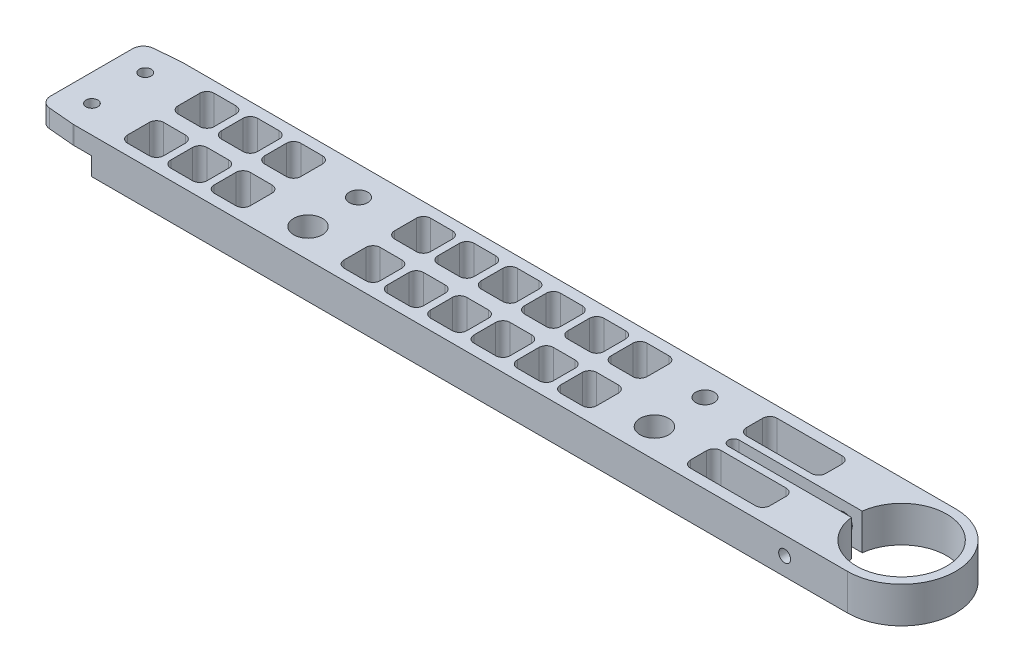
SolidWorks part; units mm, degrees
material "3.1355 (EN-AW 2024)"
ref_plane "Front" through (0, 0, 0) normal (0, 0, 1) x (1, 0, 0)
ref_plane "Top" through (0, 0, 0) normal (0, 1, 0) x (1, 0, 0)
ref_plane "Right" through (0, 0, 0) normal (1, 0, 0) x (0, 0, -1)
sketch "Эскиз1" plane through (0, 0, 0) normal (0, 1, 0) x (1, 0, 0)
  line L0 (240, 15) -> (15, 15) construction
  line L1 (15, 0) -> (240, 0)
  line L2 (0, 0) -> (0, 30) construction
  line L3 (15, 30) -> (240, 30)
  line L4 (240, 0) -> (240, 30)
  line L5 (0, 0) -> (15, 0) construction
  line L6 (0, 0.8749) -> (0, 29.1251)
  line L7 (15, 30) -> (10, 30)
  line L8 (10, 30) -> (0, 29.1251)
  line L9 (10, 0) -> (0, 0.8749)
  line L10 (15, 0) -> (10, 0)
  line L11 (0, 30) -> (1, 30) construction
  line L12 (1, 30) -> (1, 29.2126) construction
  arc A0 (15, 30) -> (15, 0) centre (15, 15) ccw construction
  point P13 (0, 15)
  dimension "D1" = 30
  dimension "D2" = 240
  dimension "D4" = 5
  dimension "D5" = 85
extrude "Бобышка-Вытянуть1" add sketch "Эскиз1" along normal blind 10
sketch "Эскиз4" plane through (0, 0, 0) normal (0, -1, 0) x (1, 0, 0)
  line L0 (10, 0) -> (240, 0) construction
  line L1 (0, -30) -> (15, -30)
  line L2 (0, -30) -> (0, 0)
  line L3 (0, 0) -> (15, 0)
  line L4 (15, -30) -> (15, 0)
  line L5 (0, -29.1251) -> (0, -0.8749) construction
  line L6 (240, -30) -> (10, -30) construction
  dimension "D1" = 15
extrude "Вырез-Вытянуть2" cut sketch "Эскиз4" against normal blind 5
fillet "Скругление1" radius 3 4 edges at (10, 7.5, -30) (0, 7.5, -29.1251) (0, 7.5, -0.8749) (10, 7.5, 0)
sketch "Эскиз5" plane through (0, 0, 0) normal (0, -1, 0) x (1, 0, 0)
  line L0 (240, -15) -> (210, -15) construction
  line L1 (240, 0) -> (240, -30) construction
  line L2 (15, -15) -> (20, -15) construction
  line L3 (15, -30) -> (15, 0) construction
  line L4 (240, -30) -> (15, -30) construction
  line L5 (22, -17) -> (28, -17)
  line L6 (20, -19) -> (20, -25)
  line L7 (22, -27) -> (28, -27)
  line L8 (30, -19) -> (30, -25)
  line L9 (20, -17) -> (30, -27) construction
  line L10 (20, -27) -> (30, -17) construction
  line L11 (34, -17) -> (40, -17)
  line L12 (32, -19) -> (32, -25)
  line L13 (34, -27) -> (40, -27)
  line L14 (42, -19) -> (42, -25)
  line L15 (32, -17) -> (42, -27) construction
  line L16 (32, -27) -> (42, -17) construction
  line L17 (46, -17) -> (52, -17)
  line L18 (44, -19) -> (44, -25)
  line L19 (46, -27) -> (52, -27)
  line L20 (54, -19) -> (54, -25)
  line L21 (44, -17) -> (54, -27) construction
  line L22 (44, -27) -> (54, -17) construction
  line L23 (58, -17) -> (64, -17)
  line L24 (56, -19) -> (56, -25)
  line L25 (58, -27) -> (64, -27)
  line L26 (66, -19) -> (66, -25)
  line L27 (56, -17) -> (66, -27) construction
  line L28 (56, -27) -> (66, -17) construction
  line L29 (70, -17) -> (76, -17)
  line L30 (68, -19) -> (68, -25)
  line L31 (70, -27) -> (76, -27)
  line L32 (78, -19) -> (78, -25)
  line L33 (68, -17) -> (78, -27) construction
  line L34 (68, -27) -> (78, -17) construction
  line L35 (82, -17) -> (88, -17)
  line L36 (80, -19) -> (80, -25)
  line L37 (82, -27) -> (88, -27)
  line L38 (90, -19) -> (90, -25)
  line L39 (80, -17) -> (90, -27) construction
  line L40 (80, -27) -> (90, -17) construction
  line L41 (94, -17) -> (100, -17)
  line L42 (92, -19) -> (92, -25)
  line L43 (94, -27) -> (100, -27)
  line L44 (102, -19) -> (102, -25)
  line L45 (92, -17) -> (102, -27) construction
  line L46 (92, -27) -> (102, -17) construction
  line L47 (106, -17) -> (112, -17)
  line L48 (104, -19) -> (104, -25)
  line L49 (106, -27) -> (112, -27)
  line L50 (114, -19) -> (114, -25)
  line L51 (104, -17) -> (114, -27) construction
  line L52 (104, -27) -> (114, -17) construction
  line L53 (118, -17) -> (124, -17)
  line L54 (116, -19) -> (116, -25)
  line L55 (118, -27) -> (124, -27)
  line L56 (126, -19) -> (126, -25)
  line L57 (116, -17) -> (126, -27) construction
  line L58 (116, -27) -> (126, -17) construction
  line L59 (130, -17) -> (136, -17)
  line L60 (128, -19) -> (128, -25)
  line L61 (130, -27) -> (136, -27)
  line L62 (138, -19) -> (138, -25)
  line L63 (128, -17) -> (138, -27) construction
  line L64 (128, -27) -> (138, -17) construction
  line L65 (142, -17) -> (148, -17)
  line L66 (140, -19) -> (140, -25)
  line L67 (142, -27) -> (148, -27)
  line L68 (150, -19) -> (150, -25)
  line L69 (140, -17) -> (150, -27) construction
  line L70 (140, -27) -> (150, -17) construction
  line L71 (154, -17) -> (160, -17)
  line L72 (152, -19) -> (152, -25)
  line L73 (154, -27) -> (160, -27)
  line L74 (162, -19) -> (162, -25)
  line L75 (152, -17) -> (162, -27) construction
  line L76 (152, -27) -> (162, -17) construction
  line L77 (166, -17) -> (172, -17)
  line L78 (164, -19) -> (164, -25)
  line L79 (166, -27) -> (172, -27)
  line L80 (174, -19) -> (174, -25)
  line L81 (164, -17) -> (174, -27) construction
  line L82 (164, -27) -> (174, -17) construction
  line L83 (178, -17) -> (184, -17)
  line L84 (176, -19) -> (176, -25)
  line L85 (178, -27) -> (184, -27)
  line L86 (186, -19) -> (186, -25)
  line L87 (176, -17) -> (186, -27) construction
  line L88 (176, -27) -> (186, -17) construction
  line L89 (190, -17) -> (196, -17)
  line L90 (188, -19) -> (188, -25)
  line L91 (190, -27) -> (196, -27)
  line L92 (198, -19) -> (198, -25)
  line L93 (188, -17) -> (198, -27) construction
  line L94 (188, -27) -> (198, -17) construction
  line L95 (202, -17) -> (208, -17)
  line L96 (200, -19) -> (200, -25)
  line L97 (202, -27) -> (208, -27)
  line L98 (210, -19) -> (210, -25)
  line L99 (200, -17) -> (210, -27) construction
  line L100 (200, -27) -> (210, -17) construction
  line L101 (25, -22) -> (37, -22) construction
  line L102 (25, -8) -> (37, -8) construction
  line L103 (200, -3) -> (210, -13) construction
  line L104 (200, -13) -> (210, -3) construction
  line L105 (188, -3) -> (198, -13) construction
  line L106 (188, -13) -> (198, -3) construction
  line L107 (176, -3) -> (186, -13) construction
  line L108 (176, -13) -> (186, -3) construction
  line L109 (164, -3) -> (174, -13) construction
  line L110 (164, -13) -> (174, -3) construction
  line L111 (152, -3) -> (162, -13) construction
  line L112 (152, -13) -> (162, -3) construction
  line L113 (140, -3) -> (150, -13) construction
  line L114 (140, -13) -> (150, -3) construction
  line L115 (128, -3) -> (138, -13) construction
  line L116 (128, -13) -> (138, -3) construction
  line L117 (116, -3) -> (126, -13) construction
  line L118 (116, -13) -> (126, -3) construction
  line L119 (104, -3) -> (114, -13) construction
  line L120 (104, -13) -> (114, -3) construction
  line L121 (92, -3) -> (102, -13) construction
  line L122 (92, -13) -> (102, -3) construction
  line L123 (80, -3) -> (90, -13) construction
  line L124 (80, -13) -> (90, -3) construction
  line L125 (68, -3) -> (78, -13) construction
  line L126 (68, -13) -> (78, -3) construction
  line L127 (56, -3) -> (66, -13) construction
  line L128 (56, -13) -> (66, -3) construction
  line L129 (44, -3) -> (54, -13) construction
  line L130 (44, -13) -> (54, -3) construction
  line L131 (32, -3) -> (42, -13) construction
  line L132 (32, -13) -> (42, -3) construction
  line L133 (20, -3) -> (30, -13) construction
  line L134 (20, -13) -> (30, -3) construction
  line L135 (210, -11) -> (210, -5)
  line L136 (202, -3) -> (208, -3)
  line L137 (200, -11) -> (200, -5)
  line L138 (202, -13) -> (208, -13)
  line L139 (198, -11) -> (198, -5)
  line L140 (190, -3) -> (196, -3)
  line L141 (188, -11) -> (188, -5)
  line L142 (190, -13) -> (196, -13)
  line L143 (186, -11) -> (186, -5)
  line L144 (178, -3) -> (184, -3)
  line L145 (176, -11) -> (176, -5)
  line L146 (178, -13) -> (184, -13)
  line L147 (174, -11) -> (174, -5)
  line L148 (166, -3) -> (172, -3)
  line L149 (164, -11) -> (164, -5)
  line L150 (166, -13) -> (172, -13)
  line L151 (162, -11) -> (162, -5)
  line L152 (154, -3) -> (160, -3)
  line L153 (152, -11) -> (152, -5)
  line L154 (154, -13) -> (160, -13)
  line L155 (150, -11) -> (150, -5)
  line L156 (142, -3) -> (148, -3)
  line L157 (140, -11) -> (140, -5)
  line L158 (142, -13) -> (148, -13)
  line L159 (138, -11) -> (138, -5)
  line L160 (130, -3) -> (136, -3)
  line L161 (128, -11) -> (128, -5)
  line L162 (130, -13) -> (136, -13)
  line L163 (126, -11) -> (126, -5)
  line L164 (118, -3) -> (124, -3)
  line L165 (116, -11) -> (116, -5)
  line L166 (118, -13) -> (124, -13)
  line L167 (114, -11) -> (114, -5)
  line L168 (106, -3) -> (112, -3)
  line L169 (104, -11) -> (104, -5)
  line L170 (106, -13) -> (112, -13)
  line L171 (102, -11) -> (102, -5)
  line L172 (94, -3) -> (100, -3)
  line L173 (92, -11) -> (92, -5)
  line L174 (94, -13) -> (100, -13)
  line L175 (90, -11) -> (90, -5)
  line L176 (82, -3) -> (88, -3)
  line L177 (80, -11) -> (80, -5)
  line L178 (82, -13) -> (88, -13)
  line L179 (78, -11) -> (78, -5)
  line L180 (70, -3) -> (76, -3)
  line L181 (68, -11) -> (68, -5)
  line L182 (70, -13) -> (76, -13)
  line L183 (66, -11) -> (66, -5)
  line L184 (58, -3) -> (64, -3)
  line L185 (56, -11) -> (56, -5)
  line L186 (58, -13) -> (64, -13)
  line L187 (54, -11) -> (54, -5)
  line L188 (46, -3) -> (52, -3)
  line L189 (44, -11) -> (44, -5)
  line L190 (46, -13) -> (52, -13)
  line L191 (42, -11) -> (42, -5)
  line L192 (34, -3) -> (40, -3)
  line L193 (32, -11) -> (32, -5)
  line L194 (34, -13) -> (40, -13)
  line L195 (30, -11) -> (30, -5)
  line L196 (22, -3) -> (28, -3)
  line L197 (20, -11) -> (20, -5)
  line L198 (22, -13) -> (28, -13)
  arc A0 (20, -25) -> (22, -27) centre (22, -25) ccw
  arc A1 (30, -25) -> (28, -27) centre (28, -25) cw
  arc A2 (28, -17) -> (30, -19) centre (28, -19) cw
  arc A3 (22, -17) -> (20, -19) centre (22, -19) ccw
  arc A4 (32, -25) -> (34, -27) centre (34, -25) ccw
  arc A5 (42, -25) -> (40, -27) centre (40, -25) cw
  arc A6 (40, -17) -> (42, -19) centre (40, -19) cw
  arc A7 (34, -17) -> (32, -19) centre (34, -19) ccw
  arc A8 (44, -25) -> (46, -27) centre (46, -25) ccw
  arc A9 (54, -25) -> (52, -27) centre (52, -25) cw
  arc A10 (52, -17) -> (54, -19) centre (52, -19) cw
  arc A11 (46, -17) -> (44, -19) centre (46, -19) ccw
  arc A12 (56, -25) -> (58, -27) centre (58, -25) ccw
  arc A13 (66, -25) -> (64, -27) centre (64, -25) cw
  arc A14 (64, -17) -> (66, -19) centre (64, -19) cw
  arc A15 (58, -17) -> (56, -19) centre (58, -19) ccw
  arc A16 (68, -25) -> (70, -27) centre (70, -25) ccw
  arc A17 (78, -25) -> (76, -27) centre (76, -25) cw
  arc A18 (76, -17) -> (78, -19) centre (76, -19) cw
  arc A19 (70, -17) -> (68, -19) centre (70, -19) ccw
  arc A20 (80, -25) -> (82, -27) centre (82, -25) ccw
  arc A21 (90, -25) -> (88, -27) centre (88, -25) cw
  arc A22 (88, -17) -> (90, -19) centre (88, -19) cw
  arc A23 (82, -17) -> (80, -19) centre (82, -19) ccw
  arc A24 (92, -25) -> (94, -27) centre (94, -25) ccw
  arc A25 (102, -25) -> (100, -27) centre (100, -25) cw
  arc A26 (100, -17) -> (102, -19) centre (100, -19) cw
  arc A27 (94, -17) -> (92, -19) centre (94, -19) ccw
  arc A28 (104, -25) -> (106, -27) centre (106, -25) ccw
  arc A29 (114, -25) -> (112, -27) centre (112, -25) cw
  arc A30 (112, -17) -> (114, -19) centre (112, -19) cw
  arc A31 (106, -17) -> (104, -19) centre (106, -19) ccw
  arc A32 (116, -25) -> (118, -27) centre (118, -25) ccw
  arc A33 (126, -25) -> (124, -27) centre (124, -25) cw
  arc A34 (124, -17) -> (126, -19) centre (124, -19) cw
  arc A35 (118, -17) -> (116, -19) centre (118, -19) ccw
  arc A36 (128, -25) -> (130, -27) centre (130, -25) ccw
  arc A37 (138, -25) -> (136, -27) centre (136, -25) cw
  arc A38 (136, -17) -> (138, -19) centre (136, -19) cw
  arc A39 (130, -17) -> (128, -19) centre (130, -19) ccw
  arc A40 (140, -25) -> (142, -27) centre (142, -25) ccw
  arc A41 (150, -25) -> (148, -27) centre (148, -25) cw
  arc A42 (148, -17) -> (150, -19) centre (148, -19) cw
  arc A43 (142, -17) -> (140, -19) centre (142, -19) ccw
  arc A44 (152, -25) -> (154, -27) centre (154, -25) ccw
  arc A45 (162, -25) -> (160, -27) centre (160, -25) cw
  arc A46 (160, -17) -> (162, -19) centre (160, -19) cw
  arc A47 (154, -17) -> (152, -19) centre (154, -19) ccw
  arc A48 (164, -25) -> (166, -27) centre (166, -25) ccw
  arc A49 (174, -25) -> (172, -27) centre (172, -25) cw
  arc A50 (172, -17) -> (174, -19) centre (172, -19) cw
  arc A51 (166, -17) -> (164, -19) centre (166, -19) ccw
  arc A52 (176, -25) -> (178, -27) centre (178, -25) ccw
  arc A53 (186, -25) -> (184, -27) centre (184, -25) cw
  arc A54 (184, -17) -> (186, -19) centre (184, -19) cw
  arc A55 (178, -17) -> (176, -19) centre (178, -19) ccw
  arc A56 (188, -25) -> (190, -27) centre (190, -25) ccw
  arc A57 (198, -25) -> (196, -27) centre (196, -25) cw
  arc A58 (196, -17) -> (198, -19) centre (196, -19) cw
  arc A59 (190, -17) -> (188, -19) centre (190, -19) ccw
  arc A60 (200, -25) -> (202, -27) centre (202, -25) ccw
  arc A61 (210, -25) -> (208, -27) centre (208, -25) cw
  arc A62 (208, -17) -> (210, -19) centre (208, -19) cw
  arc A63 (202, -17) -> (200, -19) centre (202, -19) ccw
  arc A64 (202, -13) -> (200, -11) centre (202, -11) cw
  arc A65 (208, -13) -> (210, -11) centre (208, -11) ccw
  arc A66 (210, -5) -> (208, -3) centre (208, -5) ccw
  arc A67 (200, -5) -> (202, -3) centre (202, -5) cw
  arc A68 (190, -13) -> (188, -11) centre (190, -11) cw
  arc A69 (196, -13) -> (198, -11) centre (196, -11) ccw
  arc A70 (198, -5) -> (196, -3) centre (196, -5) ccw
  arc A71 (188, -5) -> (190, -3) centre (190, -5) cw
  arc A72 (178, -13) -> (176, -11) centre (178, -11) cw
  arc A73 (184, -13) -> (186, -11) centre (184, -11) ccw
  arc A74 (186, -5) -> (184, -3) centre (184, -5) ccw
  arc A75 (176, -5) -> (178, -3) centre (178, -5) cw
  arc A76 (166, -13) -> (164, -11) centre (166, -11) cw
  arc A77 (172, -13) -> (174, -11) centre (172, -11) ccw
  arc A78 (174, -5) -> (172, -3) centre (172, -5) ccw
  arc A79 (164, -5) -> (166, -3) centre (166, -5) cw
  arc A80 (154, -13) -> (152, -11) centre (154, -11) cw
  arc A81 (160, -13) -> (162, -11) centre (160, -11) ccw
  arc A82 (162, -5) -> (160, -3) centre (160, -5) ccw
  arc A83 (152, -5) -> (154, -3) centre (154, -5) cw
  arc A84 (142, -13) -> (140, -11) centre (142, -11) cw
  arc A85 (148, -13) -> (150, -11) centre (148, -11) ccw
  arc A86 (150, -5) -> (148, -3) centre (148, -5) ccw
  arc A87 (140, -5) -> (142, -3) centre (142, -5) cw
  arc A88 (130, -13) -> (128, -11) centre (130, -11) cw
  arc A89 (136, -13) -> (138, -11) centre (136, -11) ccw
  arc A90 (138, -5) -> (136, -3) centre (136, -5) ccw
  arc A91 (128, -5) -> (130, -3) centre (130, -5) cw
  arc A92 (118, -13) -> (116, -11) centre (118, -11) cw
  arc A93 (124, -13) -> (126, -11) centre (124, -11) ccw
  arc A94 (126, -5) -> (124, -3) centre (124, -5) ccw
  arc A95 (116, -5) -> (118, -3) centre (118, -5) cw
  arc A96 (106, -13) -> (104, -11) centre (106, -11) cw
  arc A97 (112, -13) -> (114, -11) centre (112, -11) ccw
  arc A98 (114, -5) -> (112, -3) centre (112, -5) ccw
  arc A99 (104, -5) -> (106, -3) centre (106, -5) cw
  arc A100 (94, -13) -> (92, -11) centre (94, -11) cw
  arc A101 (100, -13) -> (102, -11) centre (100, -11) ccw
  arc A102 (102, -5) -> (100, -3) centre (100, -5) ccw
  arc A103 (92, -5) -> (94, -3) centre (94, -5) cw
  arc A104 (82, -13) -> (80, -11) centre (82, -11) cw
  arc A105 (88, -13) -> (90, -11) centre (88, -11) ccw
  arc A106 (90, -5) -> (88, -3) centre (88, -5) ccw
  arc A107 (80, -5) -> (82, -3) centre (82, -5) cw
  arc A108 (70, -13) -> (68, -11) centre (70, -11) cw
  arc A109 (76, -13) -> (78, -11) centre (76, -11) ccw
  arc A110 (78, -5) -> (76, -3) centre (76, -5) ccw
  arc A111 (68, -5) -> (70, -3) centre (70, -5) cw
  arc A112 (58, -13) -> (56, -11) centre (58, -11) cw
  arc A113 (64, -13) -> (66, -11) centre (64, -11) ccw
  arc A114 (66, -5) -> (64, -3) centre (64, -5) ccw
  arc A115 (56, -5) -> (58, -3) centre (58, -5) cw
  arc A116 (46, -13) -> (44, -11) centre (46, -11) cw
  arc A117 (52, -13) -> (54, -11) centre (52, -11) ccw
  arc A118 (54, -5) -> (52, -3) centre (52, -5) ccw
  arc A119 (44, -5) -> (46, -3) centre (46, -5) cw
  arc A120 (34, -13) -> (32, -11) centre (34, -11) cw
  arc A121 (40, -13) -> (42, -11) centre (40, -11) ccw
  arc A122 (42, -5) -> (40, -3) centre (40, -5) ccw
  arc A123 (32, -5) -> (34, -3) centre (34, -5) cw
  arc A124 (22, -13) -> (20, -11) centre (22, -11) cw
  arc A125 (28, -13) -> (30, -11) centre (28, -11) ccw
  arc A126 (30, -5) -> (28, -3) centre (28, -5) ccw
  arc A127 (20, -5) -> (22, -3) centre (22, -5) cw
  point P8 (25, -22)
  point P29 (37, -22)
  point P46 (49, -22)
  point P63 (61, -22)
  point P80 (73, -22)
  point P97 (85, -22)
  point P114 (97, -22)
  point P131 (109, -22)
  point P148 (121, -22)
  point P165 (133, -22)
  point P182 (145, -22)
  point P199 (157, -22)
  point P216 (169, -22)
  point P233 (181, -22)
  point P250 (193, -22)
  point P267 (205, -22)
  point P542 (205, -8)
  point P543 (193, -8)
  point P544 (181, -8)
  point P545 (169, -8)
  point P546 (157, -8)
  point P547 (145, -8)
  point P548 (133, -8)
  point P549 (121, -8)
  point P550 (109, -8)
  point P551 (97, -8)
  point P552 (85, -8)
  point P553 (73, -8)
  point P554 (61, -8)
  point P555 (49, -8)
  dimension "D5" = 2
  dimension "D1" = 30
  dimension "D2" = 5
  dimension "D3" = 10
  dimension "D4" = 3
  dimension "D7" = 12
  dimension "D6" = 16
extrude "Вырез-Вытянуть3" cut sketch "Эскиз5" against normal through all
sketch "Эскиз6" plane through (0, 0, 0) normal (0, -1, 0) x (1, 0, 0)
  line L1 (54.9134, -27.789) -> (78.7581, -27.789)
  line L2 (54.9134, -27.789) -> (54.9134, -2.1781)
  line L3 (54.9134, -2.1781) -> (78.7581, -2.1781)
  line L4 (78.7581, -27.789) -> (78.7581, -2.1781)
  line L5 (150.9148, -27.789) -> (175.2011, -27.789)
  line L6 (150.9148, -27.789) -> (150.9148, -2.1781)
  line L7 (150.9148, -2.1781) -> (175.2011, -2.1781)
  line L8 (175.2011, -27.789) -> (175.2011, -2.1781)
extrude "Бобышка-Вытянуть2" add sketch "Эскиз6" against normal through all
sketch "Эскиз7" plane through (0, 0, 0) normal (0, -1, 0) x (1, 0, 0)
  line L0 (54, -22) -> (80, -22) construction
  line L1 (54, -25) -> (54, -19) construction
  line L2 (80, -19) -> (80, -25) construction
  line L3 (54, -8) -> (80, -8) construction
  line L4 (54, -11) -> (54, -5) construction
  line L5 (80, -5) -> (80, -11) construction
  line L6 (176, -8) -> (150, -8) construction
  line L7 (176, -5) -> (176, -11) construction
  line L8 (150, -11) -> (150, -5) construction
  line L9 (176, -22) -> (150, -22) construction
  line L10 (176, -19) -> (176, -25) construction
  line L11 (150, -25) -> (150, -19) construction
  point P12 (67, -8)
  point P13 (67, -22)
  point P26 (163, -8)
  point P27 (163, -22)
hole_wizard "Отверстие обработанное метчиком 1/4-201" positions "Эскиз9" profile "Эскиз8" tap size "1/4-20" standard "Ansi Inch" end condition through all
sketch "Эскиз9" plane through (0, 0, 0) normal (0, -1, 0) x (-1, 0, 0)
  point P0 (-67, 22)
  point P3 (-163, 22)
sketch "Эскиз8" plane through (67, 0, -22) normal (1, 0, 0) x (0, 0, -1)
  line L0 (0, 0) -> (0, 10)
  line L1 (0, 10) -> (2.5527, 10)
  line L2 (2.5527, 10) -> (2.5527, 0)
  line L5 (2.5527, 0) -> (0, 0)
  line L11 (0, -6.35) -> (0, 107.95) construction
  dimension "Диаметр проходного сверла" = 5.1054
  dimension "Глубина проходного сверла" = 10
cosmetic thread "Отверстие резьбы1" parameters "D2"=6.35
cosmetic thread "Отверстие резьбы2" parameters "D2"=6.35
hole_wizard "Отверстие обработанное метчиком 3/8-161" positions "Эскиз11" profile "Эскиз10" tap size "3/8-16" standard "Ansi Inch" end condition through all
sketch "Эскиз11" plane through (0, 0, 0) normal (0, -1, 0) x (-1, 0, 0)
  point P0 (-163, 8)
  point P3 (-67, 8)
sketch "Эскиз10" plane through (163, 0, -8) normal (1, 0, 0) x (0, 0, -1)
  line L0 (0, 0) -> (0, 10)
  line L1 (0, 10) -> (3.9687, 10)
  line L2 (3.9687, 10) -> (3.9687, 0)
  line L5 (3.9687, 0) -> (0, 0)
  line L11 (0, -6.35) -> (0, 107.95) construction
  dimension "Диаметр проходного сверла" = 7.9375
  dimension "Глубина проходного сверла" = 10
cosmetic thread "Отверстие резьбы3" parameters "D2"=9.525
cosmetic thread "Отверстие резьбы4" parameters "D2"=9.525
sketch "Эскиз12" plane through (0, 0, 0) normal (0, -1, 0) x (1, 0, 0)
  line L0 (240, -15) -> (224.5, -15) construction
  line L1 (240, 0) -> (240, -30) construction
  line L2 (224.5, -30) -> (240, -30)
  line L3 (240, -30) -> (240, 0)
  line L4 (240, 0) -> (224.5, 0)
  circle A0 centre (224.5, -15) radius 12.5
  arc A1 (224.5, -30) -> (224.5, 0) centre (224.5, -15) ccw
  dimension "D2" = 25
  dimension "D1" = 15.5
extrude "Вырез-Вытянуть4" cut sketch "Эскиз12" against normal through all
sketch "Эскиз13" plane through (0, 0, 0) normal (0, -1, 0) x (1, 0, 0)
  line L1 (198.8914, -28.2833) -> (210.981, -28.2833)
  line L2 (198.8914, -28.2833) -> (198.8914, -1.8689)
  line L3 (198.8914, -1.8689) -> (210.981, -1.8689)
  line L4 (210.981, -28.2833) -> (210.981, -1.8689)
extrude "Бобышка-Вытянуть3" add sketch "Эскиз13" against normal through all
sketch "Эскиз14" plane through (0, 0, 0) normal (0, -1, 0) x (1, 0, 0)
  line L0 (212, -15) -> (178, -15) construction
  line L1 (178, -15) -> (213.598, -15) construction
  line L2 (178, -13.5) -> (213.598, -13.5)
  line L3 (178, -16.5) -> (213.598, -16.5)
  arc A0 (178, -13.5) -> (178, -16.5) centre (178, -15) ccw
  arc A1 (213.598, -16.5) -> (213.598, -13.5) centre (213.598, -15) ccw
  circle A4 centre (224.5, -15) radius 12.5 construction
  point P5 (195.799, -15)
  dimension "D2" = 1.5
  dimension "D1" = 34
extrude "Вырез-Вытянуть5" cut sketch "Эскиз14" against normal blind 10
sketch "Эскиз15" plane through (0, 0, 0) normal (0, 0, 1) x (1, 0, 0)
  line L0 (212.0903, 5) -> (207.0903, 5) construction
  line L1 (212.0903, 0) -> (212.0903, 10) construction
  dimension "D1" = 5
hole_wizard "Отверстие обработанное метчиком M4x0.71" positions "Эскиз17" profile "Эскиз16" tap size "M4x0.7" standard "Ansi Metric" end condition through all
sketch "Эскиз17" plane through (0, 0, -13.5) normal (0, 0, -1) x (-1, 0, 0)
  point P0 (-207.0903, 5)
sketch "Эскиз16" plane through (207.0903, 5, -13.5) normal (1, 0, 0) x (0, 1, 0)
  line L0 (0, 0) -> (0, 13.5)
  line L1 (0, 13.5) -> (1.65, 13.5)
  line L2 (1.65, 13.5) -> (1.65, 0)
  line L5 (1.65, 0) -> (0, 0)
  line L11 (0, -6.35) -> (0, 107.95) construction
  dimension "Диаметр проходного сверла" = 3.3
  dimension "Глубина проходного сверла" = 13.5
cosmetic thread "Отверстие резьбы5" parameters "D2"=4
hole_wizard "Цековка для винта с внутренним шестигранником M41" positions "Эскиз19" profile "Эскиз18" counterbore size "M4" standard "Ansi Metric" end condition up to next
sketch "Эскиз19" plane through (0, 0, -30) normal (0, 0, -1) x (-1, 0, 0)
  point P0 (-207.0903, 5)
sketch "Эскиз18" plane through (207.0903, 5, -30) normal (1, 0, 0) x (0, 1, 0)
  line L0 (0, 0) -> (0, 13.5)
  line L1 (0, 13.5) -> (2.25, 13.5)
  line L3 (2.25, 13.5) -> (2.25, 4)
  line L4 (2.25, 4) -> (4, 4)
  line L5 (4, 4) -> (4, 0)
  line L7 (4, 0) -> (0, 0)
  line L11 (0, -6.35) -> (0, 107.95) construction
  dimension "Диаметр сквозного отверстия" = 4.5
  dimension "Глубина сквозного отверстия" = 13.5
  dimension "Диаметр цековки" = 8
  dimension "Глубина цековки" = 4
sketch "Эскиз20" plane through (0, 5, 0) normal (0, -1, 0) x (1, 0, 0)
  line L0 (0, -15) -> (7.5, -15) construction
  line L1 (0, -3.6239) -> (0, -26.3761) construction
  line L2 (7.5, -15) -> (7.5, -0.2187) construction
  line L3 (2.7385, -0.6353) -> (9.8695, -0.0114) construction
  line L4 (7.5, -15) -> (7.5, -29.7813) construction
  line L5 (9.8695, -29.9886) -> (2.7385, -29.3647) construction
  point P4 (7.5, -22.3906)
  point P11 (7.5, -7.6094)
  dimension "D1" = 7.5
hole_wizard "Отверстие обработанное метчиком M4x0.72" [suppressed] positions "Эскиз22" profile "Эскиз21" tap size "M4x0.7" standard "Ansi Metric"
sketch "Эскиз22" plane through (0, 5, 0) normal (0, -1, 0) x (-1, 0, 0)
  point P0 (-7.5, 15)
sketch "Эскиз21" plane through (7.5, 5, -15) normal (1, 0, 0) x (0, 0, -1)
  line L0 (0, 0) -> (0, 5)
  line L1 (0, 5) -> (1.65, 5)
  line L2 (1.65, 5) -> (1.65, 0)
  line L5 (1.65, 0) -> (0, 0)
  line L11 (0, -6.35) -> (0, 107.95) construction
  dimension "Диаметр проходного сверла" = 3.3
  dimension "Глубина проходного сверла" = 5
cosmetic thread "Отверстие резьбы6" [suppressed] parameters "D2"=4
hole_wizard "Отверстие обработанное метчиком M4x0.73" positions "Эскиз25" profile "Эскиз24" tap size "M4x0.7" standard "Ansi Metric" end condition through all
sketch "Эскиз25" plane through (0, 5, 0) normal (0, -1, 0) x (-1, 0, 0)
  point P0 (-7.5, 7.6094)
  point P3 (-7.5, 22.3906)
sketch "Эскиз24" plane through (7.5, 5, -7.6094) normal (1, 0, 0) x (0, 0, -1)
  line L0 (0, 0) -> (0, 5)
  line L1 (0, 5) -> (1.65, 5)
  line L2 (1.65, 5) -> (1.65, 0)
  line L5 (1.65, 0) -> (0, 0)
  line L11 (0, -6.35) -> (0, 107.95) construction
  dimension "Диаметр проходного сверла" = 3.3
  dimension "Глубина проходного сверла" = 5
cosmetic thread "Отверстие резьбы7" parameters "D2"=4
cosmetic thread "Отверстие резьбы8" parameters "D2"=4
sketch "Эскиз23" plane through (0, 0, 0) normal (0, -1, 0) x (1, 0, 0)
  line L3 (176, -5) -> (176, -11) construction
  line L4 (178, -11.5) -> (184, -11.5)
  line L5 (178, -11.5) -> (184, -11.5)
  line L6 (186, -11) -> (186, -5) construction
  line L7 (178, -13) -> (184, -13) construction
  line L8 (176, -9.5) -> (176, -11)
  line L9 (178, -13) -> (184, -13)
  line L10 (186, -11) -> (186, -9.5)
  line L11 (186, -8) -> (188, -8) construction
  line L12 (188, -5) -> (188, -11) construction
  line L13 (187, -6.6769) -> (187, -28.5814) construction
  line L14 (176.5, -15) -> (185.5268, -15) construction
  line L16 (178, -18.5) -> (184, -18.5)
  line L17 (196, -11.5) -> (190, -11.5)
  line L18 (188, -11) -> (188, -9.5)
  line L19 (196, -13) -> (190, -13)
  line L20 (198, -9.5) -> (198, -11)
  line L21 (186, -19) -> (186, -20.5)
  line L22 (178, -17) -> (184, -17)
  line L23 (176, -20.5) -> (176, -19)
  line L24 (198, -20.5) -> (198, -19)
  line L25 (196, -17) -> (190, -17)
  line L26 (188, -19) -> (188, -20.5)
  line L27 (196, -18.5) -> (190, -18.5)
  arc A2 (178, -11.5) -> (176, -9.5) centre (178, -9.5) cw
  arc A3 (184, -11.5) -> (186, -9.5) centre (184, -9.5) ccw
  arc A4 (176, -11) -> (178, -13) centre (178, -11) ccw construction
  arc A5 (184, -13) -> (186, -11) centre (184, -11) ccw construction
  arc A6 (176, -11) -> (178, -13) centre (178, -11) ccw
  arc A7 (184, -13) -> (186, -11) centre (184, -11) ccw
  arc A8 (190, -11.5) -> (188, -9.5) centre (190, -9.5) cw
  arc A9 (190, -13) -> (188, -11) centre (190, -11) cw
  arc A10 (198, -11) -> (196, -13) centre (196, -11) cw
  arc A11 (196, -11.5) -> (198, -9.5) centre (196, -9.5) ccw
  arc A12 (178, -13.5) -> (178, -16.5) centre (178, -15) ccw construction
  arc A13 (184, -18.5) -> (186, -20.5) centre (184, -20.5) cw
  arc A14 (184, -17) -> (186, -19) centre (184, -19) cw
  arc A15 (176, -19) -> (178, -17) centre (178, -19) cw
  arc A16 (178, -18.5) -> (176, -20.5) centre (178, -20.5) ccw
  arc A17 (196, -18.5) -> (198, -20.5) centre (196, -20.5) cw
  arc A18 (198, -19) -> (196, -17) centre (196, -19) ccw
  arc A19 (190, -17) -> (188, -19) centre (190, -19) ccw
  arc A20 (190, -18.5) -> (188, -20.5) centre (190, -20.5) ccw
  dimension "D1" = 1.5
extrude "Бобышка-Вытянуть5" add sketch "Эскиз23" against normal through all
sketch "Эскиз26" plane through (0, 0, 0) normal (0, -1, 0) x (1, 0, 0)
  line L5 (186, -9.5) -> (186, -5)
  line L6 (178, -11.5) -> (184, -11.5)
  line L7 (176, -5) -> (176, -9.5)
  line L8 (184, -3) -> (178, -3)
  line L10 (178, -11.5) -> (190, -11.5)
  line L11 (176, -5) -> (176, -9.5)
  line L12 (190, -3) -> (178, -3)
  line L13 (198, -9.5) -> (198, -5)
  line L14 (190, -11.5) -> (196, -11.5)
  line L15 (188, -5) -> (188, -9.5)
  line L16 (196, -3) -> (190, -3)
  line L17 (198, -9.5) -> (198, -5)
  line L18 (190, -11.5) -> (196, -11.5)
  line L20 (196, -3) -> (190, -3)
  line L21 (176, -20.5) -> (176, -25)
  line L22 (184, -18.5) -> (178, -18.5)
  line L23 (186, -25) -> (186, -20.5)
  line L24 (178, -27) -> (184, -27)
  line L25 (176, -20.5) -> (176, -25)
  line L26 (190, -18.5) -> (178, -18.5)
  line L28 (178, -27) -> (190, -27)
  line L29 (188, -20.5) -> (188, -25)
  line L30 (196, -18.5) -> (190, -18.5)
  line L31 (198, -25) -> (198, -20.5)
  line L32 (190, -27) -> (196, -27)
  line L34 (196, -18.5) -> (190, -18.5)
  line L35 (198, -25) -> (198, -20.5)
  line L36 (190, -27) -> (196, -27)
  arc A4 (184, -11.5) -> (186, -9.5) centre (184, -9.5) ccw
  arc A5 (176, -9.5) -> (178, -11.5) centre (178, -9.5) ccw
  arc A6 (178, -3) -> (176, -5) centre (178, -5) ccw
  arc A7 (186, -5) -> (184, -3) centre (184, -5) ccw
  arc A9 (176, -9.5) -> (178, -11.5) centre (178, -9.5) ccw
  arc A10 (178, -3) -> (176, -5) centre (178, -5) ccw
  arc A12 (196, -11.5) -> (198, -9.5) centre (196, -9.5) ccw
  arc A13 (188, -9.5) -> (190, -11.5) centre (190, -9.5) ccw
  arc A14 (190, -3) -> (188, -5) centre (190, -5) ccw
  arc A15 (198, -5) -> (196, -3) centre (196, -5) ccw
  arc A16 (196, -11.5) -> (198, -9.5) centre (196, -9.5) ccw
  arc A19 (198, -5) -> (196, -3) centre (196, -5) ccw
  arc A20 (178, -18.5) -> (176, -20.5) centre (178, -20.5) ccw
  arc A21 (186, -20.5) -> (184, -18.5) centre (184, -20.5) ccw
  arc A22 (184, -27) -> (186, -25) centre (184, -25) ccw
  arc A23 (176, -25) -> (178, -27) centre (178, -25) ccw
  arc A24 (178, -18.5) -> (176, -20.5) centre (178, -20.5) ccw
  arc A27 (176, -25) -> (178, -27) centre (178, -25) ccw
  arc A28 (190, -18.5) -> (188, -20.5) centre (190, -20.5) ccw
  arc A29 (198, -20.5) -> (196, -18.5) centre (196, -20.5) ccw
  arc A30 (196, -27) -> (198, -25) centre (196, -25) ccw
  arc A31 (188, -25) -> (190, -27) centre (190, -25) ccw
  arc A33 (198, -20.5) -> (196, -18.5) centre (196, -20.5) ccw
  arc A34 (196, -27) -> (198, -25) centre (196, -25) ccw
  dimension "D1" = 0
  dimension "D2" = 0
  dimension "D3" = 0
  dimension "D4" = 0
extrude "Вырез-Вытянуть6" cut sketch "Эскиз26" against normal through all
